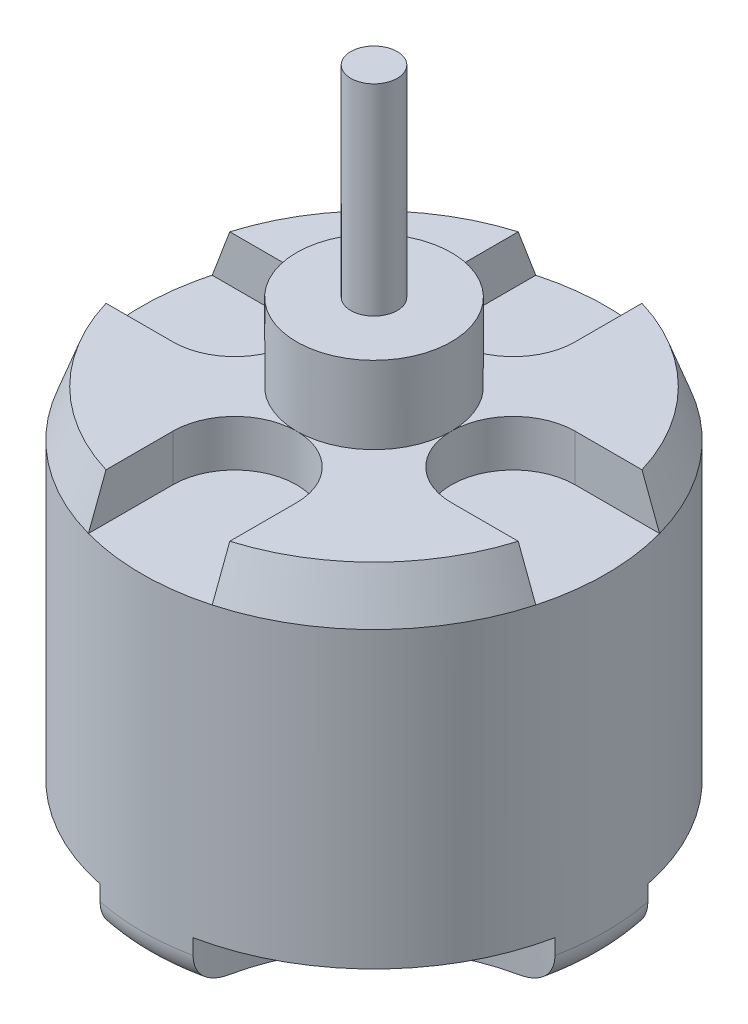
SolidWorks part; units mm, degrees
ref_plane "Plan de face" through (0, 0, 0) normal (0, 0, 1) x (1, 0, 0)
ref_plane "Plan de dessus" through (0, 0, 0) normal (0, 1, 0) x (1, 0, 0)
ref_plane "Plan de droite" through (0, 0, 0) normal (1, 0, 0) x (0, 0, -1)
sketch "Esquisse1" plane through (0, 0, 0) normal (0, 0, 1) x (1, 0, 0)
  line L0 (0, 23) -> (0, -20)
  line L1 (-1.5, -20) -> (-15, -20)
  line L2 (-15, -20) -> (-15, 5)
  line L3 (-15, 5) -> (-5, 5)
  line L4 (-5, 5) -> (-5, 10)
  line L5 (-5, 10) -> (-1.5, 10)
  line L6 (-1.5, 10) -> (-1.5, 23)
  line L7 (-1.5, 23) -> (0, 23)
  line L8 (0, -20) -> (0, -22)
  line L9 (0, -22) -> (-1.5, -22)
  line L10 (-1.5, -22) -> (-1.5, -20)
  dimension "D1" = 15
  dimension "D2" = 1.5
  dimension "D3" = 3.5
  dimension "D4" = 43
  dimension "D5" = 25
  dimension "D6" = 5
  dimension "D7" = 20
  dimension "D8" = 2
  dimension "D9" = 1.5
revolve "Révolution1" add sketch "Esquisse1" angle 360 about L0
chamfer "Chanfrein1" distance 3 angle 20 1 edges at (-15, 5, 0) first distance on face at (-15, -20, 0)
fillet "Congé1" radius 2 1 edges at (-15, -20, 0)
sketch "Esquisse2" plane through (0, 5, 0) normal (0, 1, 0) x (1, 0, 0)
  line L0 (-4, 9) -> (-4, 19)
  line L1 (-4, 19) -> (4, 19)
  line L2 (4, 19) -> (4, 9)
  line L3 (9, 4) -> (19, 4)
  line L4 (19, 4) -> (19, -4)
  line L5 (19, -4) -> (9, -4)
  line L6 (4, -9) -> (4, -19)
  line L7 (4, -19) -> (-4, -19)
  line L8 (-4, -19) -> (-4, -9)
  line L9 (-9, -4) -> (-19, -4)
  line L10 (-19, -4) -> (-19, 4)
  line L11 (-19, 4) -> (-9, 4)
  arc A0 (-4, 9) -> (4, 9) centre (0, 9) ccw
  circle A1 centre (0, 0) radius 5 construction
  arc A2 (9, 4) -> (9, -4) centre (9, 0) ccw
  arc A3 (4, -9) -> (-4, -9) centre (0, -9) ccw
  arc A4 (-9, -4) -> (-9, 4) centre (-9, 0) ccw
  dimension "D1" = 8
  dimension "D2" = 4
  dimension "D3" = 10
  dimension "D4" = 4
extrude "Enlèv. mat.-Extru.1" cut sketch "Esquisse2" against normal blind 3
sketch "Esquisse3" plane through (0, -20, 0) normal (0, -1, 0) x (1, 0, 0)
  line L0 (-3, 15) -> (-3, -15) construction
  line L1 (3, 15) -> (3, -15) construction
  line L2 (-15, 3) -> (15, 3) construction
  line L3 (-15, -3) -> (15, -3) construction
  arc A0 (-15, 3) -> (-3, 15) centre (-15, 15) ccw
  arc A1 (3, 15) -> (15, 3) centre (15, 15) ccw
  arc A2 (15, -3) -> (3, -15) centre (15, -15) ccw
  arc A3 (-15, -3) -> (-3, -15) centre (-15, -15) cw
  circle A4 centre (0, 9) radius 1.5
  circle A5 centre (0, -9) radius 1.5
  circle A6 centre (9, 0) radius 1.5
  circle A7 centre (-9, 0) radius 1.5
  arc A8 (-15, 3) -> (-3, 15) centre (-6.4869, 6.4869) cw
  arc A9 (-15, -3) -> (-3, -15) centre (-6.0335, -6.0335) ccw
  arc A10 (3, -15) -> (15, -3) centre (5.8989, -5.8989) ccw
  arc A11 (15, 3) -> (3, 15) centre (6.3169, 6.3169) ccw
  dimension "D3" = 3
  dimension "D4" = 3
  dimension "D6" = 3
  dimension "D13" = 3
  dimension "D2" = 3
  dimension "D5" = 30
  dimension "D7" = 30
  dimension "D8" = 15
  dimension "D9" = 30
  dimension "D10" = 30
  dimension "D11" = 15
  dimension "D12" = 15
  dimension "D14" = 9
  dimension "D15" = 9
  dimension "D16" = 9
  dimension "D17" = 9
extrude "Enlèv. mat.-Extru.2" cut sketch "Esquisse3" against normal blind 3
sketch "Esquisse4" plane through (0, -20, 0) normal (0, -1, 0) x (1, 0, 0)
  circle A0 centre (0, 0) radius 1.5
  circle A1 centre (0, 0) radius 5
  dimension "D1" = 10
extrude "Enlèv. mat.-Extru.3" cut sketch "Esquisse4" against normal blind 1
